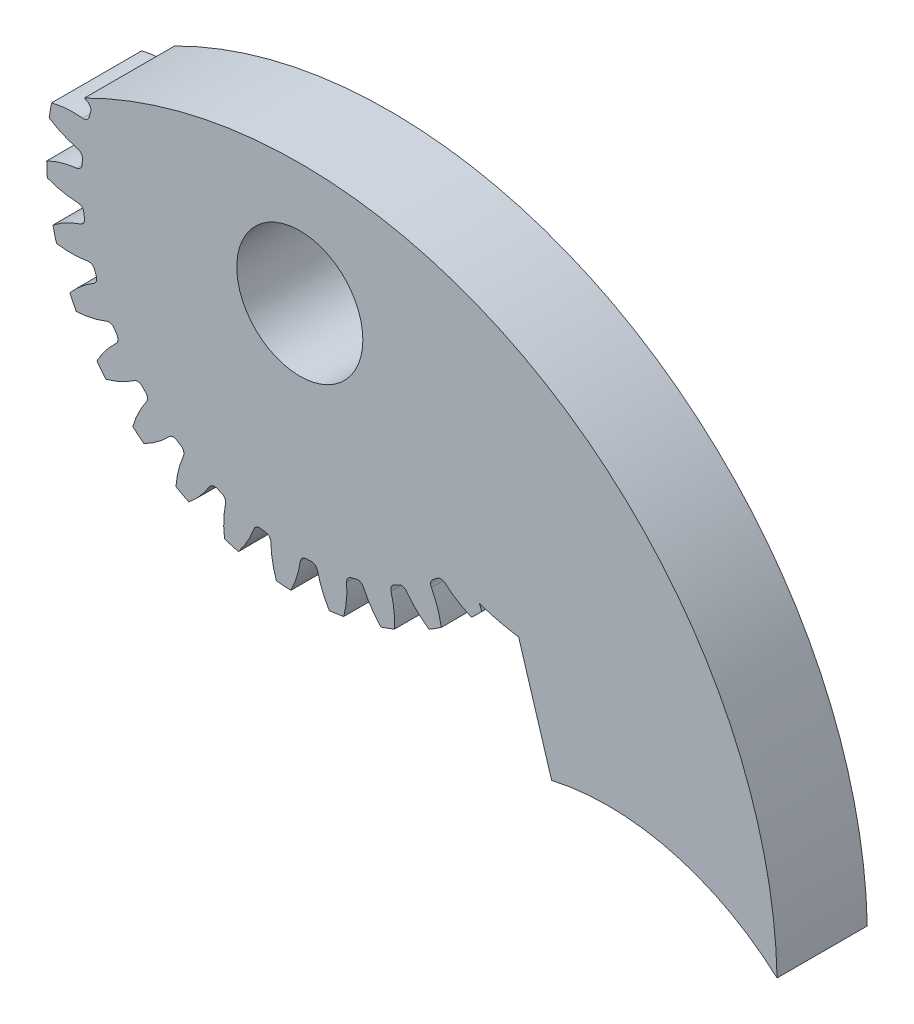
SolidWorks part; units mm, degrees
material "ABS"
ref_plane "Front" through (0, 0, 0) normal (0, 0, 1) x (1, 0, 0)
ref_plane "Top" through (0, 0, 0) normal (0, 1, 0) x (1, 0, 0)
ref_plane "Right" through (0, 0, 0) normal (1, 0, 0) x (0, 0, -1)
sketch "Sketch3" plane through (0, 0, 0) normal (0, 0, 1) x (1, 0, 0)
  circle A0 centre (0, 0) radius 40.64
  dimension "od" = 81.28
extrude "gearBody" add sketch "Sketch3" along normal blind 9.652
sketch "Sketch2" plane through (0, 0, 0) normal (0, 0, 1) x (1, 0, 0)
  line L0 (0, 0) -> (34.0786, 14.1158) construction
  line L1 (45.4751, -11.4855) -> (0, 0) construction
  line L2 (0, 0) -> (36.3143, 0) construction
  line L3 (38.0972, -0.458) -> (37.8451, -4.4001) construction
  line L5 (37.9712, -2.4291) -> (0, 0) construction
  line L7 (0, 0) -> (36.8864, 0) construction
  arc A0 (36.879, -0.7403) -> (36.6727, -3.9649) centre (0, 0) ccw construction
  arc A1 (40.637, 0.4947) -> (40.2427, -5.6687) centre (0, 0) ccw construction
  arc A2 (38.0972, -0.458) -> (37.8451, -4.4001) centre (0, 0) ccw construction
  arc A3 (34.9015, -2.6404) -> (34.9534, -1.8283) centre (0, 0) ccw
  arc A4 (45.4751, -11.4855) -> (35.6466, -3.6712) centre (32.0022, -18.3431) ccw
  arc A5 (45.4751, -11.4855) -> (46.5679, 5.5974) centre (0, 0) ccw
  arc A6 (46.5679, 5.5974) -> (35.8238, -0.9008) centre (34.0786, 14.1158) cw
  arc A7 (34.9534, -1.8283) -> (35.8238, -0.9008) centre (35.9376, -1.8798) cw
  arc A8 (35.6466, -3.6712) -> (34.9015, -2.6404) centre (35.8842, -2.7147) cw
  point P6 (46.5679, 5.5974)
  point P22 (45.4751, -11.4855)
  dimension "baseDia" = 73.7729
  dimension "od" = 81.28
  dimension "pd" = 76.2
  dimension "rd" = 70.0024
  dimension "rFillet" = 0.9855
  dimension "pointX" = 46.5679
  dimension "pointY" = 5.5974
  dimension "CTT" = 3.9421
  dimension "flankCenterAngle" = 22.5
extrude "toothCut" cut sketch "Sketch2" along normal through all
pattern_circular "CirPattern1" count 30 over 360 about axis through (0, 0, 9.652) along (0, 0, -1) of "toothCut"
scale "Scale1" scale about centroid uniform scaling no x scale factor 0.666667 y scale factor 0.666667 z scale factor 1
sketch "hub1Dia" plane through (0, 0, 0) normal (0, 0, -1) x (-1, 0, 0)
  circle A0 centre (0, 0) radius 12.7
  dimension "hub1Dia" = 25.4
sketch "hub2Dia" plane through (0, 0, 9.652) normal (0, 0, 1) x (1, 0, 0)
  circle A0 centre (0, 0) radius 12.7
  dimension "hub2dia" = 25.4
sketch "boreDia" plane through (0, 0, 0) normal (0, 0, 1) x (1, 0, 0)
  circle A0 centre (0, 0) radius 6.7469
  dimension "boreDia" = 13.4937
extrude "bore" cut sketch "boreDia" against normal mid plane 25400
sketch "Sketch4" plane through (0, 0, 9.652) normal (0, 0, 1) x (1, 0, 0)
  circle A0 centre (0, -38.1) radius 51.1048
  arc A2 (-27.9892, 4.6587) -> (27.9892, 4.6587) centre (0, 0) cw
  dimension "D1" = 102.2096
  dimension "D2" = 38.1
extrude "Cut-Extrude1" cut sketch "Sketch4" against normal through all contours A0 region at (0, 17.6405, 9.652)
sketch "Sketch5" plane through (0, 0, 9.652) normal (0, 0, 1) x (1, 0, 0)
  line L0 (0, -38.1) -> (51.1048, -38.1) construction
  line L1 (0, 0) -> (0, -38.1) construction
  line L2 (0, -38.1) -> (-25.5524, 6.1581) construction
  line L3 (0, -38.1) -> (44.2581, -63.6524) construction
  line L4 (23.4248, -19.2156) -> (26.9592, -30.742)
  circle A0 centre (0, -38.1) radius 51.1048 construction
  arc A1 (21.891, 8.0789) -> (-23.0664, 7.5031) centre (0, -38.1) ccw construction
  circle A2 centre (0, -38.1) radius 14.3933 construction
  circle A3 centre (32.9956, -57.15) radius 27.0891 construction
  arc A4 (26.9592, -30.742) -> (51.0928, -36.9929) centre (32.9956, -57.15) cw
  arc A5 (51.0928, -36.9929) -> (8.2583, 12.3331) centre (0, -38.1) ccw
  spline S0 degree 2 poles (8.2583, 12.3331) (3.9786, -16.3376) (23.4248, -19.2156) knots 0 0 0 1 1 1
  point P18 (14.6053, -13.7571)
  point P20 (23.4248, -19.2156)
  point P21 (18.7554, -18.026)
  dimension "D2" = 28.7867
  dimension "D4" = 54.1782
  dimension "D1" = 120
  dimension "D3" = 120
  dimension "D5" = 38.1
extrude "Boss-Extrude1" add sketch "Sketch5" against normal up to surface (9.652 mm away) up to face at (6.7469, 0, 0)
equation "\"Aft_Section_Length\" = 30in"
equation "\"Mid_Coupler_Length\" = 12in"
equation "\"AB_Coupler_OD_Length\"= 1in"
equation "\"AB_Coupling_Section_Length\"= 0.375in"
equation "\"AB_Coupler_Length\"= \"AB_Coupler_OD_Length\" + \"AB_Coupling_Section_Length\" * 2"
equation "\"Cutout_Angle\" = 60"
equation "\"AB_Paddle_Height\" = 0.375in"
equation "\"AB_Coupler_Num_Screws\"= 4"
equation "\"Num_Cutouts\" = 4"
equation "\"AB_Coupler_OD\"= 4.024in"
equation "\"AB_Coupler_ID\"= 3.7in"
equation "\"AB_Coupler_Surface_Diameter\"= 3.899in"
equation "\"AB_Coupling_Screw_Diameter\"= 0.1065in"
equation "\"AB_Central_Bushing_Length\" = 0.75in"
equation "\"Lead_Screw_Dist\" = 2in"
equation "\"Lead_Screw_Diam\" = 0.375in"
equation "\"Lead_Screw_Length\" = \"Mid_Coupler_Length\" + 2*0.375in + 2*0.5in"
equation "\"Paddle_Pin_Offset\" = 0.25in"
equation "\"Paddle_Pin_Radius\" = 2.25*2/3in"
equation "\"Fwd_BKHD_From_Top\" = 18in"
equation "\"D1@Sketch4\" = \"Body_Tube_OD\""
equation "\"D2@Sketch4\"=\"Paddle_Pin_Radius\""
equation "\"Motor_OD\" = 54mm"
equation "\"Paddle_Gear_OD\" = 3.2in"
equation "\"Drive_Gear_OD\" = 1.7*2/3in"
equation "\"Fin_Thickness\" = 0.118in"
equation "\"DB9_Hole_Dist\" = 25mm"
equation "\"Motor_Length\" = 401mm"
equation "\"Body_Tube_OD\"= 4.024in"
equation "\"Body_Tube_ID\"= 3.90in"
equation "\"Coupler_OD\" = 3.899in"
equation "\"Coupler_ID\" = 3.755in"
equation "\"Fwd_Section_Length\" = 25in"
equation "\"Mid_Section_Length\" = 6in"
equation "\"Aft_Upper_Tube_Length\" = 10in"
equation "\"Aft_Lower_Tube_Length\" = 18in"
equation "\"Nosecone_Coupler_Length\" = 5in"
equation "\"Avionics_Bulkhead_Thickness\" = 0.25in"
equation "\"Avionics_Bulkhead_Lip\" = 0.125in"
equation "\"Avionics_Board_Length\" = \"Mid_Coupler_Length\" - 2*\"Avionics_Bulkhead_Lip\""
equation "\"Lead_Screw_Hole_Diam\" = (27/64)*1in"
equation "\"Centering_Ring_Cutout_Dia\"=1.5in"
equation "\"Airbrakes_Wire_Hole_Dist\" = 1.1in"
equation "\"Airbrakes_Wire_Hole_Dia\" = 0.25in"
equation "\"DB9_Relief_Width\" = 0.47in"
equation "\"DB9_Relief_Hole_Offset\" = 0.09in"
equation "\"Servo_Gear_Offset\" = 0.5in"
equation "\"D2@Sketch5\"=\"Drive_Gear_OD\""
equation "\"D5@Sketch5\"=\"Paddle_Pin_Radius\""
